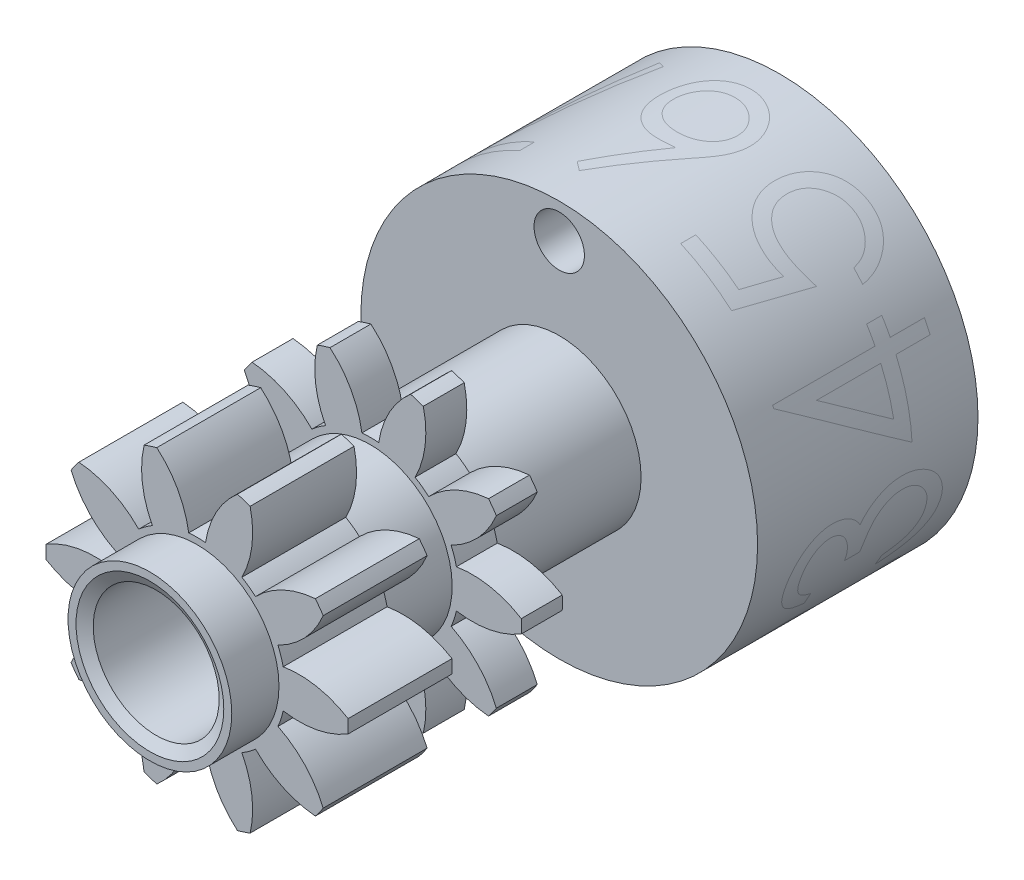
SolidWorks part; units mm, degrees
ref_plane "Front Plane" through (0, 0, 0) normal (0, 0, 1) x (1, 0, 0)
ref_plane "Top Plane" through (0, 0, 0) normal (0, 1, 0) x (1, 0, 0)
ref_plane "Right Plane" through (0, 0, 0) normal (1, 0, 0) x (0, 0, -1)
sketch "Sketch1" plane through (0, 0, 0) normal (0, 0, 1) x (1, 0, 0)
  circle A0 centre (0, 0) radius 1.3
  dimension "D1" = 2.6
extrude "Boss-Extrude1" add sketch "Sketch1" against normal blind 10
sketch "Sketch2" plane through (0, 0, -10) normal (0, 0, -1) x (-1, 0, 0)
  circle A0 centre (0, 0) radius 3.15
  dimension "D1" = 6.3
extrude "Boss-Extrude2" add sketch "Sketch2" against normal offset from surface (3.5 mm away) 6.5 up to face at (1.3, 0, 0)
sketch "Sketch3" plane through (0, 0, -10) normal (0, 0, -1) x (-1, 0, 0)
  circle A0 centre (0, 0) radius 1.75
  dimension "D1" = 3.5
extrude "Boss-Extrude3" add sketch "Sketch3" along normal offset from surface (0.2 mm away) 10.2 up to face at (1.3, 0, 0)
sketch "Sketch4" plane through (0, 0, 0) normal (1, 0, 0) x (0, 0, -1)
  line L0 (0, 0) -> (10.2, 0) construction
  line L1 (10.2, -1.75) -> (10.2, 1.75) construction
  line L2 (0, 1.3) -> (0, -1.3) construction
  line L3 (3.5, -1.3) -> (4.15, -1.3)
  line L4 (3.5, -1.3) -> (3.5, -2.4)
  line L5 (3.5, -2.4) -> (4.15, -2.4)
  line L6 (4.15, -1.3) -> (4.15, -2.4)
  line L7 (0, -1.3) -> (6.5, -1.3) construction
  line L9 (0.75, -1.3) -> (2.4, -1.3)
  line L10 (0.75, -1.3) -> (0.75, -2.4)
  line L11 (0.75, -2.4) -> (2.4, -2.4)
  line L12 (2.4, -1.3) -> (2.4, -2.4)
  dimension "D1" = 3.5
  dimension "D2" = 4.15
  dimension "D3" = 4.8
  dimension "D4" = 0.75
  dimension "D5" = 2.4
revolve "Revolve1" add sketch "Sketch4" angle 360 about L0
sketch "Sketch5" plane through (0, 0, 0) normal (0, 0, 1) x (1, 0, 0)
  circle A0 centre (0, 0) radius 1
  dimension "D1" = 2
extrude "Cut-Extrude1" cut sketch "Sketch5" against normal through all
chamfer "Chamfer1" distance 0.1 angle 45 1 edges at (1.75, 0, -10.2)
sketch "Sketch6" plane through (0, 0, 0) normal (1, 0, 0) x (0, 0, -1)
  line L0 (0, 0) -> (10.2, 0) construction
  line L1 (10.2, -1.65) -> (10.2, 1.65) construction
  line L2 (10.2, 1.4) -> (7.7751, 0)
  line L3 (7.7751, 0) -> (10.2, 0)
  line L4 (10.2, 0) -> (10.2, 1.4)
  dimension "D1" = 30
  dimension "D2" = 2.8
revolve "Cut-Revolve1" cut sketch "Sketch6" angle 360 about L0
chamfer "Chamfer2" distance 0.1 angle 60 1 edges at (1, 0, 0) first distance on face at (1, 0, 0)
sketch "Sketch7" plane through (0, 0, -6.5) normal (0, 0, 1) x (1, 0, 0)
  line L0 (0, 0) -> (0, 3.15) construction
  circle A0 centre (0, 2.6) radius 0.4
  circle A1 centre (0, 0) radius 3.15 construction
  dimension "D1" = 0.8
  dimension "D2" = 2.6
extrude "Cut-Extrude2" cut sketch "Sketch7" against normal up to next
sketch "Sketch8" plane through (0, 0, -0.75) normal (0, 0, 1) x (1, 0, 0)
  line L0 (0, 0) -> (0, 2.4) construction
  line L1 (0, 0) -> (-0.618, 1.9021) construction
  line L2 (0, 0) -> (0.618, 1.9021) construction
  line L3 (0, 0) -> (-2.4, 0) construction
  line L4 (0, 0) -> (-1.618, -1.1756) construction
  circle A0 centre (0, 0) radius 2.4 construction
  circle A1 centre (0, 0) radius 2 construction
  arc A2 (0.6402, -2.313) -> (0.134, -1.3936) centre (1.618, -1.1756) cw
  arc A3 (-0.134, -1.3936) -> (0.134, -1.3936) centre (0, 0) ccw
  arc A4 (-0.6402, -2.313) -> (-0.134, -1.3936) centre (-1.618, -1.1756) ccw
  arc A5 (-0.6402, -2.313) -> (0.6402, -2.313) centre (0, 0) ccw
  dimension "D1" = 4
  dimension "D4" = 2.8
  dimension "D6" = 3
  dimension "D2" = 18
  dimension "D3" = 18
  dimension "D5" = 36
extrude "Cut-Extrude3" cut sketch "Sketch8" against normal up to surface (3.4 mm away) up to face at (-1.3, 0, -4.15)
pattern_circular "CirPattern1" count 10 over 360 about axis through (0, 0, -10.2) along (0, 0, 1) of "Cut-Extrude3"
sketch "Sketch10" plane through (0, 0, -0.75) normal (0, 0, 1) x (1, 0, 0)
  line L0 (0, 0) -> (1.6068, 2.2116) construction
  circle A0 centre (0, 0) radius 1.9874 construction
  circle A1 centre (1.6068, 2.2116) radius 0.7463
  arc A2 (0.7107, 1.2062) -> (0.8416, 2.2476) centre (-0.618, 1.9021) ccw construction
  arc A3 (1.8775, 1.495) -> (0.9275, 1.0487) centre (2, 0) ccw construction
  dimension "D1" = 3.48
sketch "Sketch11" plane through (0, 0, -3.5) normal (0, 0, 1) x (1, 0, 0)
  line L0 (0, 0) -> (-4.5553, -6.2698) construction
  line L1 (0, 0) -> (-3.15, 0) construction
  circle A0 centre (0, 0) radius 3.15 construction
  circle A1 centre (-3.703, -5.0968) radius 5
  point P9 (-0.7641, -1.0517)
  dimension "D2" = 10
  dimension "D1" = 54
  dimension "D3" = 1.3
extrude "Cut-Extrude4" cut sketch "Sketch11" against normal up to next contours A1
sketch "Sketch12" plane through (0, 0, -10) normal (0, 0, -1) x (-1, 0, 0)
  line L0 (0, 0) -> (0, 3.15) construction
  line L1 (0, 0) -> (1.8515, 2.5484) construction
  line L2 (0, 0) -> (2.9958, 0.9734) construction
  line L3 (0, 0) -> (2.9958, -0.9734) construction
  line L4 (0, 0) -> (1.8515, -2.5484) construction
  line L5 (0, 0) -> (0, -3.15) construction
  line L6 (0, 0) -> (-1.8515, -2.5484) construction
  line L7 (0, 0) -> (-2.9958, -0.9734) construction
  line L8 (0, 0) -> (-2.9958, 0.9734) construction
  line L9 (0, 0) -> (-1.8515, 2.5484) construction
  circle A0 centre (0, 0) radius 3.15 construction
  point P17 (0, 0)
  dimension "D1" = 10
ref_plane "Plane2" through (0, 3.15, -10) normal (0, 1, 0) x (1, 0, 0)
sketch "Sketch14" plane through (0, 3.15, -10) normal (0, 1, 0) x (1, 0, 0)
  line L0 (0, 0) -> (0, -3.5) construction
  line L1 (-0.675, -0.5) -> (0.675, -0.5)
  line L2 (-0.675, -0.5) -> (-0.675, -2.85)
  line L3 (-0.675, -2.85) -> (0.675, -2.85)
  line L4 (0.675, -0.5) -> (0.675, -2.85)
  line L5 (-3.15, -3.5) -> (3.15, -3.5) construction
  line L6 (0, 0) -> (1.8515, 0) construction
  line L7 (-2.5, -0.5) -> (2.5, -0.5)
  dimension "D1" = 0.5
  dimension "D2" = 2.35
  dimension "D3" = 1.35
  dimension "D4" = 5
sketch "Sketch20" plane through (0, 3.15, -10) normal (0, 1, 0) x (1, 0, 0)
  text T0 "6" font "Century Gothic" height 2.35
wrap "Wrap2" sketch "Sketch20" wrap type scribe source sketch "Sketch20" face at (-3.15, 0, -10)
ref_plane "Plane3" through (1.8515, 2.5484, -10) normal (0.5878, 0.809, 0) x (0.809, -0.5878, 0)
sketch "Sketch21" plane through (1.8515, 2.5484, -10) normal (0.5878, 0.809, 0) x (0.809, -0.5878, 0)
  line L0 (0, 0) -> (0, -3.5) construction
  line L1 (-1.3, -3.5) -> (1.3, -3.5) construction
  line L3 (-1, -0.5) -> (1, -0.5) construction
  line L4 (0, 0) -> (1.8515, 0) construction
  text T0 "5" font "Century Gothic" height 2.35
  dimension "D1" = 2
  dimension "D2" = 0.5
wrap "Wrap3" sketch "Sketch21" wrap type scribe source sketch "Sketch21" face at (-3.15, 0, -10)
ref_plane "Plane4" through (2.9958, 0.9734, -10) normal (0.9511, 0.309, 0) x (0, 0, -1)
sketch "Sketch22" plane through (2.9958, 0.9734, -10) normal (0.9511, 0.309, 0) x (0, 0, -1)
  line L0 (0, 0) -> (-3.5, 0) construction
  line L1 (-3.5, 3.15) -> (-3.5, -3.15) construction
  line L2 (-0.5, 1) -> (-0.5, -1) construction
  line L3 (0, 0) -> (0, -1.8515) construction
  text T0 "4" font "Century Gothic" height 2.35
  dimension "D1" = 2
  dimension "D2" = 0.5
wrap "Wrap4" sketch "Sketch22" wrap type scribe source sketch "Sketch22" face at (1.8301, 2.528, -8.2739)
ref_plane "Plane5" through (2.9958, -0.9734, -10) normal (0.9511, -0.309, 0) x (0, 0, -1)
sketch "Sketch24" plane through (2.9958, -0.9734, -10) normal (0.9511, -0.309, 0) x (0, 0, -1)
  line L0 (0, 0) -> (-3.5, 0) construction
  line L1 (-3.5, 3.15) -> (-3.5, -3.15) construction
  line L2 (-0.5, 1) -> (-0.5, -1) construction
  line L3 (0, 0) -> (0, -1.8515) construction
  text T0 "3" font "Century Gothic" height 2.35
  dimension "D1" = 0.5
  dimension "D2" = 2
wrap "Wrap5" sketch "Sketch24" wrap type scribe source sketch "Sketch24" face at (1.8301, 2.528, -8.2739)
ref_plane "Plane6" through (1.8515, -2.5484, -10) normal (0.5878, -0.809, 0) x (-0.809, -0.5878, 0)
sketch "Sketch25" plane through (1.8515, -2.5484, -10) normal (0.5878, -0.809, 0) x (-0.809, -0.5878, 0)
  line L0 (0, 0) -> (0, -3.5) construction
  line L1 (-3.15, -3.5) -> (3.15, -3.5) construction
  line L2 (-1, -0.5) -> (1, -0.5) construction
  line L3 (0, 0) -> (1.8515, 0) construction
  text T0 "2" font "Century Gothic" height 2.35
  point P8 (0, -0.5)
  dimension "D1" = 2
  dimension "D2" = 0.5
wrap "Wrap6" sketch "Sketch25" wrap type scribe source sketch "Sketch25" face at (1.8301, 2.528, -8.2739)
ref_plane "Plane7" through (0, -3.15, -10) normal (0, -1, 0) x (-1, 0, 0)
sketch "Sketch26" plane through (0, -3.15, -10) normal (0, -1, 0) x (-1, 0, 0)
  line L0 (0, 0) -> (0, -3.5) construction
  line L1 (-3.15, -3.5) -> (3.15, -3.5) construction
  line L2 (-1, -0.5) -> (1, -0.5) construction
  line L3 (0, 0) -> (1.8515, 0) construction
  text T0 "1" font "Century Gothic" height 2.35
  point P8 (0, -0.5)
  dimension "D1" = 2
  dimension "D2" = 0.5
wrap "Wrap7" sketch "Sketch26" wrap type scribe source sketch "Sketch26" face at (1.8301, 2.528, -8.2739)
ref_plane "Plane8" through (-1.8515, -2.5484, -10) normal (-0.5878, -0.809, 0) x (-0.809, 0.5878, 0)
sketch "Sketch27" plane through (-1.8515, -2.5484, -10) normal (-0.5878, -0.809, 0) x (-0.809, 0.5878, 0)
  line L0 (0, 0) -> (0, -3.5) construction
  line L1 (-3.15, -3.5) -> (3.15, -3.5) construction
  line L2 (-1, -0.5) -> (1, -0.5) construction
  line L3 (0, 0) -> (1.8515, 0) construction
  text T0 "0" font "Century Gothic" height 2.35
  point P8 (0, -0.5)
  dimension "D1" = 0.5
  dimension "D2" = 2
wrap "Wrap8" sketch "Sketch27" wrap type scribe source sketch "Sketch27" face at (1.8301, 2.528, -8.2739)
ref_plane "Plane9" through (-2.9958, -0.9734, -10) normal (-0.9511, -0.309, 0) x (0, 0, 1)
sketch "Sketch28" plane through (-2.9958, -0.9734, -10) normal (-0.9511, -0.309, 0) x (0, 0, 1)
  line L0 (0, 0) -> (3.5, 0) construction
  line L1 (3.5, -3.15) -> (3.5, 3.15) construction
  line L2 (0.5, -1) -> (0.5, 1) construction
  line L3 (0, 0) -> (0, 1.8515) construction
  text T0 "9" font "Century Gothic" height 2.35
  point P8 (0.5, 0)
  dimension "D1" = 2
  dimension "D2" = 0.5
wrap "Wrap9" sketch "Sketch28" wrap type scribe source sketch "Sketch28" face at (-1.8048, -2.5201, -8.3255)
ref_plane "Plane10" through (-2.9958, 0.9734, -10) normal (-0.9511, 0.309, 0) x (0, 0, 1)
sketch "Sketch29" plane through (-2.9958, 0.9734, -10) normal (-0.9511, 0.309, 0) x (0, 0, 1)
  line L0 (0, 0) -> (3.5, 0) construction
  line L1 (3.5, -3.15) -> (3.5, 3.15) construction
  line L2 (0.5, -1) -> (0.5, 1) construction
  line L3 (0, 0) -> (0, -1.8515) construction
  text T0 "8" font "Century Gothic" height 2.35
  point P8 (0.5, 0)
  dimension "D1" = 0.5
  dimension "D2" = 2
wrap "Wrap10" sketch "Sketch29" wrap type scribe source sketch "Sketch29" face at (-1.8048, -2.5201, -8.3255)
ref_plane "Plane11" through (-1.8515, 2.5484, -10) normal (-0.5878, 0.809, 0) x (0.809, 0.5878, 0)
sketch "Sketch30" plane through (-1.8515, 2.5484, -10) normal (-0.5878, 0.809, 0) x (0.809, 0.5878, 0)
  line L0 (0, 0) -> (0, -3.5) construction
  line L1 (-3.15, -3.5) -> (3.15, -3.5) construction
  line L2 (-1, -0.5) -> (1, -0.5) construction
  line L4 (0, 0) -> (2.9958, 0) construction
  text T0 "7" font "Century Gothic" height 2.35
  point P9 (0, -0.5)
  dimension "D1" = 2
  dimension "D2" = 0.5
wrap "Wrap11" sketch "Sketch30" wrap type scribe source sketch "Sketch30" face at (-1.8048, -2.5201, -8.3255)
